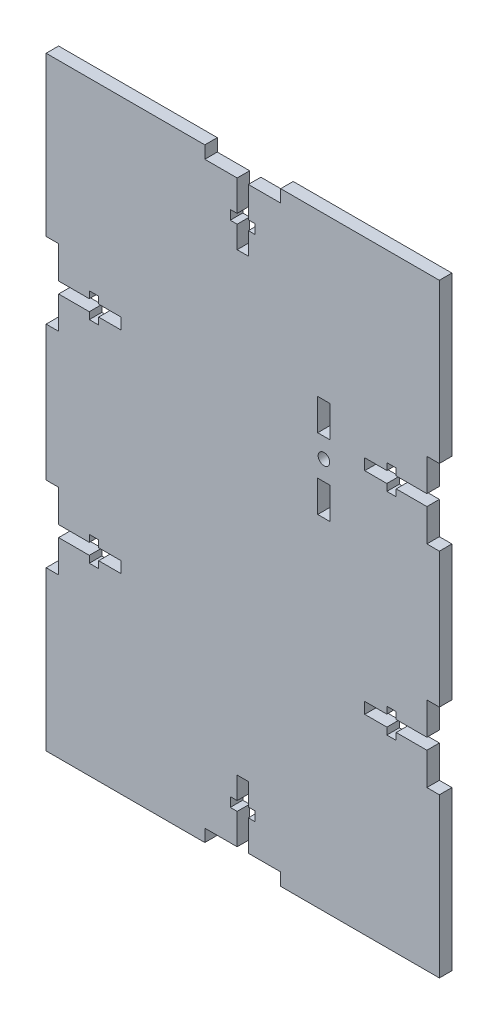
SolidWorks part; units mm, degrees
ref_plane "Front Plane" through (0, 0, 0) normal (0, 0, 1) x (1, 0, 0)
ref_plane "Top Plane" through (0, 0, 0) normal (0, 1, 0) x (1, 0, 0)
ref_plane "Right Plane" through (0, 0, 0) normal (1, 0, 0) x (0, 0, -1)
sketch "Sketch1" plane through (0, 0, 0) normal (0, 0, 1) x (1, 0, 0)
  line L0 (-50, 76.825) -> (-16.6667, 76.825)
  line L1 (-50, -76.825) -> (50, -76.825)
  line L2 (-50, -76.825) -> (-50, 76.825)
  line L3 (-50, 76.825) -> (50, 76.825) construction
  line L4 (50, -76.825) -> (50, 76.825)
  line L5 (-50, -76.825) -> (50, 76.825) construction
  line L6 (-50, 76.825) -> (50, -76.825) construction
  line L7 (-16.6667, 76.825) -> (16.6667, 76.825)
  line L8 (16.6667, 76.825) -> (50, 76.825)
  point P0 (0, 0)
  dimension "D1" = 100
  dimension "D2" = 153.65
extrude "Boss-Extrude1" add sketch "Sketch1" along normal blind 3.18
sketch "Sketch3" [suppressed] plane through (0, 0, 0) normal (0, 0, -1) x (-1, 0, 0)
  line L0 (-32.675, 34.075) -> (-32.675, -61.675)
  line L1 (-32.675, -61.675) -> (32.675, -61.675)
  line L2 (32.675, -61.675) -> (32.675, 34.075)
  line L3 (32.675, 34.075) -> (9.5, 34.075)
  line L4 (9.5, 34.075) -> (9.5, 37.075)
  line L5 (9.5, 37.075) -> (-9.5, 37.075)
  line L6 (-9.5, 37.075) -> (-9.5, 34.075)
  line L7 (-9.5, 34.075) -> (-32.675, 34.075)
  line L8 (32.675, 44.075) -> (-32.675, 44.075)
  line L9 (32.675, -61.675) -> (32.675, 44.075)
  line L10 (-32.675, -61.675) -> (32.675, -61.675)
  line L11 (-32.675, 44.075) -> (-32.675, -61.675)
  line L12 (-32.675, -61.675) -> (-32.675, -73.645) construction
  line L13 (44.645, -73.645) -> (-44.645, -73.645) construction
  line L14 (-32.675, -61.675) -> (-44.645, -61.675) construction
  line L15 (-44.645, -73.645) -> (-44.645, 73.645) construction
  line L16 (32.675, -61.675) -> (44.645, -61.675) construction
  line L17 (44.645, 73.645) -> (44.645, -73.645) construction
  dimension "D1" = 65.35
  dimension "D2" = 95.75
  dimension "D3" = 105.75
  dimension "D4" = 19
  dimension "D5" = 3
extrude "Cut-Extrude1" [suppressed] cut sketch "Sketch3" against normal through all contours L6 L7 L0 L1 L2 L3 L4 L5
sketch "Sketch9" [suppressed] plane through (-44.645, 0, 0) normal (-1, 0, 0) x (0, 0, 1)
  line L0 (0, 0) -> (3.18, 0) construction
  line L1 (0, 73.645) -> (0, -73.645) construction
  line L2 (3.18, 73.645) -> (3.18, -73.645) construction
  line L4 (0, -9.65) -> (3.18, -9.65)
  line L5 (0, -9.65) -> (0, 9.65)
  line L6 (0, 9.65) -> (3.18, 9.65)
  line L7 (3.18, -9.65) -> (3.18, 9.65)
  line L8 (0, -9.65) -> (3.18, 9.65) construction
  line L9 (0, 9.65) -> (3.18, -9.65) construction
  point P6 (1.59, 0)
  dimension "D1" = 19.3
extrude "Boss-Extrude4" [suppressed] add sketch "Sketch9" along normal blind 3.18
sketch "Sketch10" [suppressed] plane through (0, 0, 3.18) normal (0, 0, 1) x (1, 0, 0)
  line L0 (-46.235, 9.65) -> (-46.235, -9.65) construction
  line L1 (-47.825, 9.65) -> (-44.645, 9.65) construction
  line L2 (-47.825, -9.65) -> (-44.645, -9.65) construction
  circle A0 centre (-46.235, 0) radius 1.425
extrude "Cut-Extrude4" [suppressed] cut sketch "Sketch10" against normal through all
mirror "Mirror1" [suppressed] about plane through (0, 0, 0) normal (1, 0, 0)
sketch "Sketch18" [suppressed] plane through (44.645, 0, 0) normal (1, 0, 0) x (0, 0, -1)
  line L0 (0, 0) -> (-3.18, 0) construction
  line L1 (0, -73.645) -> (0, 73.645) construction
  line L2 (-3.18, -73.645) -> (-3.18, 73.645) construction
  line L4 (-3.18, -9.65) -> (0, -9.65)
  line L5 (-3.18, -9.65) -> (-3.18, 9.65)
  line L6 (-3.18, 9.65) -> (0, 9.65)
  line L7 (0, -9.65) -> (0, 9.65)
  line L8 (-3.18, -9.65) -> (0, 9.65) construction
  line L9 (-3.18, 9.65) -> (0, -9.65) construction
  point P6 (-1.59, 0)
  dimension "D1" = 19.3
extrude "Boss-Extrude8" [suppressed] add sketch "Sketch18" along normal blind 3.18
sketch "Sketch19" [suppressed] plane through (0, 0, 3.18) normal (0, 0, 1) x (1, 0, 0)
  line L0 (46.235, -9.65) -> (46.235, 9.65) construction
  line L1 (47.825, -9.65) -> (44.645, -9.65) construction
  line L2 (47.825, 9.65) -> (44.645, 9.65) construction
  circle A0 centre (46.235, 0) radius 1.425
extrude "Cut-Extrude8" [suppressed] cut sketch "Sketch19" against normal through all
mirror "Mirror2" [suppressed] about plane through (0, 0, 0) normal (1, 0, 0)
sketch "Sketch20" plane through (0, 0, 3.18) normal (0, 0, 1) x (1, 0, 0)
  line L0 (0, 70.465) -> (0, 0) construction
  line L1 (50, 76.825) -> (-50, 76.825) construction
  line L2 (-9.65, 76.825) -> (9.65, 76.825)
  line L3 (9.65, 76.825) -> (9.65, 73.645)
  line L4 (9.65, 73.645) -> (1.425, 73.645)
  line L5 (1.425, 73.645) -> (1.425, 65.845)
  line L6 (1.425, 65.845) -> (3.175, 65.845)
  line L7 (3.175, 65.845) -> (3.175, 63.465)
  line L8 (3.175, 63.465) -> (1.425, 63.465)
  line L9 (1.425, 63.465) -> (1.425, 57.845)
  line L10 (1.425, 57.845) -> (-1.425, 57.845)
  line L11 (-1.425, 57.845) -> (-1.425, 63.465)
  line L12 (-1.425, 63.465) -> (-3.175, 63.465)
  line L13 (-3.175, 63.465) -> (-3.175, 65.845)
  line L14 (-3.175, 65.845) -> (-1.425, 65.845)
  line L15 (-1.425, 65.845) -> (-1.425, 73.645)
  line L16 (-1.425, 73.645) -> (-9.65, 73.645)
  line L17 (-9.65, 73.645) -> (-9.65, 76.825)
  dimension "D1" = 19.3
  dimension "D2" = 3.18
  dimension "D3" = 15.8
  dimension "D4" = 6.35
  dimension "D5" = 2.38
  dimension "D6" = 2.85
  dimension "D7" = 7.8
extrude "Cut-Extrude9" cut sketch "Sketch20" against normal through all
mirror "Mirror3" about plane through (0, 0, 0) normal (0, 1, 0) of "Cut-Extrude9"
sketch "Sketch23" plane through (0, 0, 3.18) normal (0, 0, 1) x (1, 0, 0)
  line L0 (-50, 17.175) -> (-50, 36.475)
  line L1 (-50, 76.825) -> (-50, -76.825) construction
  line L2 (-50, 36.475) -> (-46.82, 36.475)
  line L3 (-46.82, 36.475) -> (-46.82, 28.25)
  line L4 (-46.82, 28.25) -> (-39.02, 28.25)
  line L5 (-39.02, 28.25) -> (-39.02, 30)
  line L6 (-39.02, 30) -> (-36.64, 30)
  line L7 (-36.64, 30) -> (-36.64, 28.25)
  line L8 (-36.64, 28.25) -> (-31.02, 28.25)
  line L9 (-31.02, 28.25) -> (-31.02, 25.4)
  line L10 (-31.02, 25.4) -> (-36.64, 25.4)
  line L11 (-36.64, 25.4) -> (-36.64, 23.65)
  line L12 (-36.64, 23.65) -> (-39.02, 23.65)
  line L13 (-39.02, 23.65) -> (-39.02, 25.4)
  line L14 (-39.02, 25.4) -> (-46.82, 25.4)
  line L15 (-46.82, 25.4) -> (-46.82, 17.175)
  line L16 (-46.82, 17.175) -> (-50, 17.175)
  line L17 (-9.65, 76.825) -> (-50, 76.825) construction
  line L19 (-31.02, 26.825) -> (-50, 26.825) construction
  line L20 (-50, -36.475) -> (-50, -17.175)
  line L21 (-50, -17.175) -> (-46.82, -17.175)
  line L22 (-46.82, -17.175) -> (-46.82, -25.4)
  line L23 (-46.82, -25.4) -> (-39.02, -25.4)
  line L24 (-39.02, -25.4) -> (-39.02, -23.65)
  line L25 (-39.02, -23.65) -> (-36.64, -23.65)
  line L26 (-36.64, -23.65) -> (-36.64, -25.4)
  line L27 (-36.64, -25.4) -> (-31.02, -25.4)
  line L28 (-31.02, -25.4) -> (-31.02, -28.25)
  line L29 (-31.02, -28.25) -> (-36.64, -28.25)
  line L30 (-36.64, -28.25) -> (-36.64, -30)
  line L31 (-36.64, -30) -> (-39.02, -30)
  line L32 (-39.02, -30) -> (-39.02, -28.25)
  line L33 (-39.02, -28.25) -> (-46.82, -28.25)
  line L34 (-46.82, -28.25) -> (-46.82, -36.475)
  line L35 (-46.82, -36.475) -> (-50, -36.475)
  line L36 (-50, -26.825) -> (-31.02, -26.825) construction
  line L37 (-50, -76.825) -> (-9.65, -76.825) construction
  dimension "D1" = 50
  dimension "D2" = 19.3
  dimension "D3" = 3.18
  dimension "D4" = 15.8
  dimension "D5" = 6.35
  dimension "D6" = 2.85
  dimension "D7" = 7.8
  dimension "D8" = 2.38
  dimension "D9" = 19.3
  dimension "D10" = 3.18
  dimension "D11" = 7.8
  dimension "D12" = 15.8
  dimension "D13" = 6.35
  dimension "D14" = 2.85
  dimension "D15" = 2.38
  dimension "D16" = 50
  dimension "D17" = 1.75
extrude "Cut-Extrude10" cut sketch "Sketch23" against normal through all
sketch "Sketch24" [suppressed] plane through (0, 0, 3.18) normal (0, 0, 1) x (1, 0, 0)
  line L0 (44.645, -13.995) -> (44.645, -33.295)
  line L1 (44.645, -73.645) -> (44.645, 73.645) construction
  line L2 (44.645, -33.295) -> (41.465, -33.295)
  line L3 (41.465, -33.295) -> (41.465, -25.07)
  line L4 (41.465, -25.07) -> (33.665, -25.07)
  line L5 (33.665, -25.07) -> (33.665, -26.82)
  line L6 (33.665, -26.82) -> (31.285, -26.82)
  line L7 (31.285, -26.82) -> (31.285, -25.07)
  line L8 (31.285, -25.07) -> (25.665, -25.07)
  line L9 (25.665, -25.07) -> (25.665, -22.22)
  line L10 (25.665, -22.22) -> (31.285, -22.22)
  line L11 (31.285, -22.22) -> (31.285, -20.47)
  line L12 (31.285, -20.47) -> (33.665, -20.47)
  line L13 (33.665, -20.47) -> (33.665, -22.22)
  line L14 (33.665, -22.22) -> (41.465, -22.22)
  line L15 (41.465, -22.22) -> (41.465, -13.995)
  line L16 (41.465, -13.995) -> (44.645, -13.995)
  line L17 (25.665, -23.645) -> (44.645, -23.645) construction
  line L18 (-44.645, -73.645) -> (44.645, -73.645) construction
  line L19 (44.645, 33.295) -> (44.645, 13.995)
  line L20 (44.645, 13.995) -> (41.465, 13.995)
  line L21 (41.465, 13.995) -> (41.465, 22.22)
  line L22 (41.465, 22.22) -> (33.665, 22.22)
  line L23 (33.665, 22.22) -> (33.665, 20.47)
  line L24 (33.665, 20.47) -> (31.285, 20.47)
  line L25 (31.285, 20.47) -> (31.285, 22.22)
  line L26 (31.285, 22.22) -> (25.665, 22.22)
  line L27 (25.665, 22.22) -> (25.665, 25.07)
  line L28 (25.665, 25.07) -> (31.285, 25.07)
  line L29 (31.285, 25.07) -> (31.285, 26.82)
  line L30 (31.285, 26.82) -> (33.665, 26.82)
  line L31 (33.665, 26.82) -> (33.665, 25.07)
  line L32 (33.665, 25.07) -> (41.465, 25.07)
  line L33 (41.465, 25.07) -> (41.465, 33.295)
  line L34 (41.465, 33.295) -> (44.645, 33.295)
  line L35 (25.665, 23.645) -> (44.645, 23.645) construction
  line L36 (44.645, 73.645) -> (-44.645, 73.645) construction
  dimension "D1" = 19.3
  dimension "D2" = 3.18
  dimension "D3" = 15.8
  dimension "D4" = 7.8
  dimension "D5" = 6.35
  dimension "D6" = 2.85
  dimension "D7" = 2.38
  dimension "D8" = 50
  dimension "D9" = 19.3
  dimension "D10" = 3.18
  dimension "D11" = 7.8
  dimension "D12" = 15.8
  dimension "D13" = 6.35
  dimension "D14" = 2.85
  dimension "D15" = 2.38
  dimension "D16" = 50
extrude "Cut-Extrude11" [suppressed] cut sketch "Sketch24" against normal through all
sketch "Sketch25" [suppressed] plane through (0, 0, 3.18) normal (0, 0, 1) x (1, 0, 0)
  line L0 (9.65, -73.645) -> (-9.65, -73.645)
  line L1 (-44.645, -73.645) -> (44.645, -73.645) construction
  line L2 (-9.65, -73.645) -> (-9.65, -70.465)
  line L3 (-9.65, -70.465) -> (-1.425, -70.465)
  line L4 (-1.425, -70.465) -> (-1.425, -62.665)
  line L5 (-1.425, -62.665) -> (-3.175, -62.665)
  line L6 (-3.175, -62.665) -> (-3.175, -60.285)
  line L7 (-3.175, -60.285) -> (-1.425, -60.285)
  line L8 (-1.425, -60.285) -> (-1.425, -54.665)
  line L9 (-1.425, -54.665) -> (1.425, -54.665)
  line L10 (1.425, -54.665) -> (1.425, -60.285)
  line L11 (1.425, -60.285) -> (3.175, -60.285)
  line L12 (3.175, -60.285) -> (3.175, -62.665)
  line L13 (3.175, -62.665) -> (1.425, -62.665)
  line L14 (1.425, -62.665) -> (1.425, -70.465)
  line L15 (1.425, -70.465) -> (9.65, -70.465)
  line L16 (9.65, -70.465) -> (9.65, -73.645)
  line L17 (0, -73.645) -> (0, 0) construction
  dimension "D1" = 19.3
  dimension "D2" = 3.18
  dimension "D3" = 15.8
  dimension "D4" = 7.8
  dimension "D5" = 6.35
  dimension "D6" = 2.85
  dimension "D7" = 2.38
extrude "Cut-Extrude12" [suppressed] cut sketch "Sketch25" against normal through all
sketch "Sketch26" [suppressed] plane through (0, 0, 3.18) normal (0, 0, 1) x (1, 0, 0)
  line L0 (-9.65, 73.645) -> (9.65, 73.645)
  line L1 (44.645, 73.645) -> (-44.645, 73.645) construction
  line L2 (9.65, 73.645) -> (9.65, 70.465)
  line L3 (9.65, 70.465) -> (1.425, 70.465)
  line L4 (1.425, 70.465) -> (1.425, 62.665)
  line L5 (1.425, 62.665) -> (3.175, 62.665)
  line L6 (3.175, 62.665) -> (3.175, 60.285)
  line L7 (3.175, 60.285) -> (1.425, 60.285)
  line L8 (1.425, 60.285) -> (1.425, 54.665)
  line L9 (1.425, 54.665) -> (-1.425, 54.665)
  line L10 (-1.425, 54.665) -> (-1.425, 60.285)
  line L11 (-1.425, 60.285) -> (-3.175, 60.285)
  line L12 (-3.175, 60.285) -> (-3.175, 62.665)
  line L13 (-3.175, 62.665) -> (-1.425, 62.665)
  line L14 (-1.425, 62.665) -> (-1.425, 70.465)
  line L15 (-1.425, 70.465) -> (-9.65, 70.465)
  line L16 (-9.65, 70.465) -> (-9.65, 73.645)
  line L17 (0, 73.645) -> (0, -4.4192) construction
  dimension "D1" = 19.3
  dimension "D2" = 3.18
  dimension "D3" = 7.8
  dimension "D4" = 15.8
  dimension "D5" = 6.35
  dimension "D6" = 2.85
  dimension "D7" = 2.38
extrude "Cut-Extrude13" [suppressed] cut sketch "Sketch26" against normal through all
mirror "Mirror4" about plane through (0, 0, 0) normal (1, 0, 0) of "Cut-Extrude10"
mirror "Mirror5" [suppressed] about plane through (0, 0, 0) normal (1, 0, 0)
mirror "Mirror6" [suppressed] about plane through (0, 0, 0) normal (0, 1, 0)
mirror "Mirror7" [suppressed] about plane through (0, 0, 0) normal (0, 1, 0)
sketch "Sketch27" [suppressed] plane through (-44.645, 0, 0) normal (-1, 0, 0) x (0, 0, 1)
  line L0 (0, -36.475) -> (0, -17.175)
  line L1 (0, 73.645) -> (0, -73.645) construction
  line L2 (0, -17.175) -> (3.18, -17.175)
  line L3 (3.18, 73.645) -> (3.18, -73.645) construction
  line L4 (3.18, -17.175) -> (3.18, -36.475)
  line L5 (3.18, -36.475) -> (0, -36.475)
  line L6 (3.18, -26.825) -> (0, -26.825) construction
  line L7 (3.18, -73.645) -> (0, -73.645) construction
  dimension "D1" = 19.3
  dimension "D2" = 46.82
extrude "Boss-Extrude9" [suppressed] add sketch "Sketch27" along normal blind 3.18
sketch "Sketch28" [suppressed] plane through (0, -73.645, 0) normal (0, -1, 0) x (1, 0, 0)
  line L0 (9.65, 0) -> (-9.65, 0)
  line L1 (-44.645, 0) -> (44.645, 0) construction
  line L2 (-9.65, 0) -> (-9.65, 3.18)
  line L3 (-44.645, 3.18) -> (44.645, 3.18) construction
  line L4 (-9.65, 3.18) -> (9.65, 3.18)
  line L5 (9.65, 3.18) -> (9.65, 0)
  line L6 (0, 0) -> (0, 3.18) construction
  dimension "D1" = 19.3
extrude "Boss-Extrude10" [suppressed] add sketch "Sketch28" along normal blind 3.18
sketch "Sketch29" [suppressed] plane through (0, 0, 3.18) normal (0, 0, 1) x (1, 0, 0)
  line L0 (-47.825, -26.825) -> (-37.3062, -26.825) construction
  line L1 (-47.825, -36.475) -> (-47.825, -17.175) construction
  line L2 (-46.235, -17.175) -> (-46.235, -36.475) construction
  line L3 (-47.825, -17.175) -> (-44.645, -17.175) construction
  line L4 (-47.825, -36.475) -> (-44.645, -36.475) construction
  circle A0 centre (-46.235, -26.825) radius 1.425
extrude "Cut-Extrude14" [suppressed] cut sketch "Sketch29" against normal through all
sketch "Sketch30" [suppressed] plane through (0, 0, 3.18) normal (0, 0, 1) x (1, 0, 0)
  line L0 (0, -76.825) -> (0, -66.2855) construction
  line L1 (9.65, -76.825) -> (-9.65, -76.825) construction
  line L2 (9.65, -75.235) -> (-9.65, -75.235) construction
  line L3 (9.65, -76.825) -> (9.65, -73.645) construction
  line L4 (-9.65, -76.825) -> (-9.65, -73.645) construction
  circle A0 centre (0, -75.235) radius 1.425
extrude "Cut-Extrude15" [suppressed] cut sketch "Sketch30" against normal through all
mirror "Mirror8" [suppressed] about plane through (0, 0, 0) normal (1, 0, 0)
mirror "Mirror9" [suppressed] about plane through (0, 0, 0) normal (0, 1, 0)
sketch "Sketch31" [suppressed] plane through (0, 0, 3.18) normal (0, 0, 1) x (1, 0, 0)
  line L0 (14.341, -8.1358) -> (14.341, -12.6358) construction
  line L8 (5.175, -1.9558) -> (5.175, 19.3642) construction
  line L10 (-24.825, 19.3642) -> (-24.825, -1.9558) construction
  line L11 (5.175, 19.3642) -> (-24.825, 19.3642) construction
  line L16 (23.507, -9.6358) -> (39.341, -9.6358) construction
  line L17 (23.507, 19.3642) -> (23.507, -9.6358) construction
  line L18 (39.341, 19.3642) -> (23.507, 19.3642) construction
  line L19 (39.341, -9.6358) -> (39.341, 19.3642) construction
  line L26 (14.341, -15.8158) -> (14.341, -12.6358) construction
  line L29 (-24.825, -1.9558) -> (5.175, -1.9558) construction
  line L34 (20.5772, -7.1358) -> (20.5772, 11.3642) construction
  line L35 (20.5772, 11.3642) -> (8.1048, 11.3642) construction
  line L36 (8.1048, 11.3642) -> (8.1048, -7.1358) construction
  line L37 (9.7431, -8.1358) -> (18.9389, -8.1358) construction
  line L38 (14.341, -15.8158) -> (14.341, -50) construction
  line L39 (-17.325, 9.65) -> (-24.825, 9.65) construction
  line L40 (-6.159, -12.4758) -> (34.841, -12.4758)
  line L41 (-6.159, -12.4758) -> (-6.159, -15.9758)
  line L42 (-6.159, -15.9758) -> (34.841, -15.9758)
  line L43 (34.841, -12.4758) -> (34.841, -15.9758)
  line L88 (-44.645, -50) -> (-9.65, -50) construction
  line L89 (-9.65, -50) -> (-9.65, -46.82) construction
  line L90 (-9.65, -46.82) -> (-1.425, -46.82) construction
  line L91 (-1.425, -46.82) -> (-1.425, -39.02) construction
  line L92 (-1.425, -39.02) -> (-3.175, -39.02) construction
  line L93 (-3.175, -39.02) -> (-3.175, -36.64) construction
  line L94 (-3.175, -36.64) -> (-1.425, -36.64) construction
  line L95 (-1.425, -36.64) -> (-1.425, -31.02) construction
  line L96 (-1.425, -31.02) -> (1.425, -31.02) construction
  line L97 (1.425, -31.02) -> (1.425, -36.64) construction
  line L98 (1.425, -36.64) -> (3.175, -36.64) construction
  line L99 (3.175, -36.64) -> (3.175, -39.02) construction
  line L100 (3.175, -39.02) -> (1.425, -39.02) construction
  line L101 (1.425, -39.02) -> (1.425, -46.82) construction
  line L102 (1.425, -46.82) -> (9.65, -46.82) construction
  line L103 (9.65, -46.82) -> (9.65, -50) construction
  line L104 (9.65, -50) -> (44.645, -50) construction
  line L105 (44.645, -50) -> (44.645, -9.65) construction
  line L106 (44.645, -9.65) -> (47.825, -9.65) construction
  line L107 (47.825, -9.65) -> (47.825, 9.65) construction
  line L108 (47.825, 9.65) -> (44.645, 9.65) construction
  line L109 (44.645, 9.65) -> (44.645, 50) construction
  line L110 (44.645, 50) -> (9.65, 50) construction
  line L111 (9.65, 50) -> (9.65, 46.82) construction
  line L112 (9.65, 46.82) -> (1.425, 46.82) construction
  line L113 (1.425, 46.82) -> (1.425, 39.02) construction
  line L114 (1.425, 39.02) -> (3.175, 39.02) construction
  line L115 (3.175, 39.02) -> (3.175, 36.64) construction
  line L116 (3.175, 36.64) -> (1.425, 36.64) construction
  line L117 (1.425, 36.64) -> (1.425, 31.02) construction
  line L118 (1.425, 31.02) -> (-1.425, 31.02) construction
  line L119 (-1.425, 31.02) -> (-1.425, 36.64) construction
  line L120 (-1.425, 36.64) -> (-3.175, 36.64) construction
  line L121 (-3.175, 36.64) -> (-3.175, 39.02) construction
  line L122 (-3.175, 39.02) -> (-1.425, 39.02) construction
  line L123 (-1.425, 39.02) -> (-1.425, 46.82) construction
  line L124 (-1.425, 46.82) -> (-9.65, 46.82) construction
  line L125 (-9.65, 46.82) -> (-9.65, 50) construction
  line L126 (-9.65, 50) -> (-44.645, 50) construction
  line L127 (-44.645, 50) -> (-44.645, 9.65) construction
  line L128 (-44.645, 9.65) -> (-47.825, 9.65) construction
  line L129 (-47.825, 9.65) -> (-47.825, -9.65) construction
  line L130 (-47.825, -9.65) -> (-44.645, -9.65) construction
  line L131 (-44.645, -9.65) -> (-44.645, -50) construction
  line L132 (-6.159, -12.4758) -> (34.841, -15.9758) construction
  line L133 (-6.159, -15.9758) -> (34.841, -12.4758) construction
  line L134 (-17.325, 9.65) -> (-17.325, -1.9558) construction
  line L135 (31.3061, 4.8642) -> (39.341, 4.8642) construction
  line L136 (31.3061, 4.8642) -> (31.3061, 19.3642) construction
  line L137 (-17.325, 9.65) -> (-4.325, 9.65) construction
  circle A0 centre (-17.325, 9.65) radius 1.5
  circle A1 centre (31.3061, 4.8642) radius 1.5
  circle A2 centre (-4.325, 9.65) radius 1.5
  spline S4 degree 3 poles (8.1048, -7.1358) (8.1048, -7.3148) (8.1799, -7.485) (8.4092, -7.7556) (8.5582, -7.8571) (8.8762, -8.0081) (9.0479, -8.0586) (9.3919, -8.1221) (9.5665, -8.1358) (9.7431, -8.1358) knots 0 0 0 0 0.25 0.25 0.5 0.5 0.75 0.75 1 1 1 1 construction
  spline S5 degree 3 poles (18.9389, -8.1358) (19.1156, -8.1358) (19.2906, -8.1221) (19.6363, -8.0581) (19.8071, -8.0076) (20.1239, -7.857) (20.2729, -7.7556) (20.5025, -7.4843) (20.5772, -7.3148) (20.5772, -7.1358) knots 0 0 0 0 0.25 0.25 0.5 0.5 0.75 0.75 1 1 1 1 construction
  point P14 (14.341, -14.2258)
  point P46 (-44.645, 73.645)
  dimension "D6" = 3
  dimension "D4" = 41
  dimension "D5" = 3.5
  dimension "D7" = 7.5
  dimension "D9" = 13
extrude "Cut-Extrude16" [suppressed] cut sketch "Sketch31" against normal through all contours L41 L40 L43 L42 | A1 | A2 | A0
sketch "Sketch32" plane through (0, 0, 3.18) normal (0, 0, 1) x (1, 0, 0)
  line L0 (22.24, 17.7829) -> (22.24, 9.7829)
  line L1 (22.24, 35.7829) -> (22.24, 27.7829)
  line L2 (22.24, 35.7829) -> (19.06, 35.7829)
  line L3 (22.24, 35.7829) -> (22.24, 27.7829)
  line L4 (22.24, 27.7829) -> (19.06, 27.7829)
  line L5 (19.06, 35.7829) -> (19.06, 27.7829)
  line L6 (22.24, 17.7829) -> (19.06, 17.7829)
  line L7 (22.24, 17.7829) -> (22.24, 9.7829)
  line L8 (22.24, 9.7829) -> (19.06, 9.7829)
  line L9 (19.06, 17.7829) -> (19.06, 9.7829)
  line L10 (22.24, 17.7829) -> (22.24, 27.7829) construction
  line L11 (50, -17.175) -> (50, 17.175) construction
  line L12 (50, 17.175) -> (46.82, 17.175) construction
  line L13 (46.82, 17.175) -> (46.82, 25.4) construction
  line L14 (46.82, 25.4) -> (39.02, 25.4) construction
  line L15 (39.02, 25.4) -> (39.02, 23.65) construction
  line L16 (39.02, 23.65) -> (36.64, 23.65) construction
  line L17 (36.64, 23.65) -> (36.64, 25.4) construction
  line L18 (36.64, 25.4) -> (31.02, 25.4) construction
  line L19 (31.02, 25.4) -> (31.02, 28.25) construction
  line L20 (31.02, 28.25) -> (36.64, 28.25) construction
  line L21 (36.64, 28.25) -> (36.64, 30) construction
  line L22 (36.64, 30) -> (39.02, 30) construction
  line L23 (39.02, 30) -> (39.02, 28.25) construction
  line L24 (39.02, 28.25) -> (46.82, 28.25) construction
  line L25 (46.82, 28.25) -> (46.82, 36.475) construction
  line L26 (46.82, 36.475) -> (50, 36.475) construction
  line L27 (50, 36.475) -> (50, 76.825) construction
  line L28 (50, 76.825) -> (9.65, 76.825) construction
  line L29 (9.65, 76.825) -> (9.65, 73.645) construction
  line L30 (9.65, 73.645) -> (1.425, 73.645) construction
  line L31 (1.425, 73.645) -> (1.425, 65.845) construction
  line L32 (1.425, 65.845) -> (3.175, 65.845) construction
  line L33 (3.175, 65.845) -> (3.175, 63.465) construction
  line L34 (3.175, 63.465) -> (1.425, 63.465) construction
  line L35 (1.425, 63.465) -> (1.425, 57.845) construction
  line L36 (1.425, 57.845) -> (-1.425, 57.845) construction
  line L37 (-1.425, 57.845) -> (-1.425, 63.465) construction
  line L38 (-1.425, 63.465) -> (-3.175, 63.465) construction
  line L39 (-3.175, 63.465) -> (-3.175, 65.845) construction
  line L40 (-3.175, 65.845) -> (-1.425, 65.845) construction
  line L41 (-1.425, 65.845) -> (-1.425, 73.645) construction
  line L42 (-1.425, 73.645) -> (-9.65, 73.645) construction
  line L43 (-9.65, 73.645) -> (-9.65, 76.825) construction
  line L44 (-9.65, 76.825) -> (-50, 76.825) construction
  line L45 (-50, 76.825) -> (-50, 36.475) construction
  line L46 (-50, 36.475) -> (-46.82, 36.475) construction
  line L47 (-46.82, 36.475) -> (-46.82, 28.25) construction
  line L48 (-46.82, 28.25) -> (-39.02, 28.25) construction
  line L49 (-39.02, 28.25) -> (-39.02, 30) construction
  line L50 (-39.02, 30) -> (-36.64, 30) construction
  line L51 (-36.64, 30) -> (-36.64, 28.25) construction
  line L52 (-36.64, 28.25) -> (-31.02, 28.25) construction
  line L53 (-31.02, 28.25) -> (-31.02, 25.4) construction
  line L54 (-31.02, 25.4) -> (-36.64, 25.4) construction
  line L55 (-36.64, 25.4) -> (-36.64, 23.65) construction
  line L56 (-36.64, 23.65) -> (-39.02, 23.65) construction
  line L57 (-39.02, 23.65) -> (-39.02, 25.4) construction
  line L58 (-39.02, 25.4) -> (-46.82, 25.4) construction
  line L59 (-46.82, 25.4) -> (-46.82, 17.175) construction
  line L60 (-46.82, 17.175) -> (-50, 17.175) construction
  line L61 (-50, 17.175) -> (-50, -17.175) construction
  line L62 (-50, -17.175) -> (-46.82, -17.175) construction
  line L63 (-46.82, -17.175) -> (-46.82, -25.4) construction
  line L64 (-46.82, -25.4) -> (-39.02, -25.4) construction
  line L65 (-39.02, -25.4) -> (-39.02, -23.65) construction
  line L66 (-39.02, -23.65) -> (-36.64, -23.65) construction
  line L67 (-36.64, -23.65) -> (-36.64, -25.4) construction
  line L68 (-36.64, -25.4) -> (-31.02, -25.4) construction
  line L69 (-31.02, -25.4) -> (-31.02, -28.25) construction
  line L70 (-31.02, -28.25) -> (-36.64, -28.25) construction
  line L71 (-36.64, -28.25) -> (-36.64, -30) construction
  line L72 (-36.64, -30) -> (-39.02, -30) construction
  line L73 (-39.02, -30) -> (-39.02, -28.25) construction
  line L74 (-39.02, -28.25) -> (-46.82, -28.25) construction
  line L75 (-46.82, -28.25) -> (-46.82, -36.475) construction
  line L76 (-46.82, -36.475) -> (-50, -36.475) construction
  line L77 (-50, -36.475) -> (-50, -76.825) construction
  line L78 (-50, -76.825) -> (-9.65, -76.825) construction
  line L79 (-9.65, -76.825) -> (-9.65, -73.645) construction
  line L80 (-9.65, -73.645) -> (-1.425, -73.645) construction
  line L81 (-1.425, -73.645) -> (-1.425, -65.845) construction
  line L82 (-1.425, -65.845) -> (-3.175, -65.845) construction
  line L83 (-3.175, -65.845) -> (-3.175, -63.465) construction
  line L84 (-3.175, -63.465) -> (-1.425, -63.465) construction
  line L85 (-1.425, -63.465) -> (-1.425, -57.845) construction
  line L86 (-1.425, -57.845) -> (1.425, -57.845) construction
  line L87 (1.425, -57.845) -> (1.425, -63.465) construction
  line L88 (1.425, -63.465) -> (3.175, -63.465) construction
  line L89 (3.175, -63.465) -> (3.175, -65.845) construction
  line L90 (3.175, -65.845) -> (1.425, -65.845) construction
  line L91 (1.425, -65.845) -> (1.425, -73.645) construction
  line L92 (1.425, -73.645) -> (9.65, -73.645) construction
  line L93 (9.65, -73.645) -> (9.65, -76.825) construction
  line L94 (9.65, -76.825) -> (50, -76.825) construction
  line L95 (50, -76.825) -> (50, -36.475) construction
  line L96 (50, -36.475) -> (46.82, -36.475) construction
  line L97 (46.82, -36.475) -> (46.82, -28.25) construction
  line L98 (46.82, -28.25) -> (39.02, -28.25) construction
  line L99 (39.02, -28.25) -> (39.02, -30) construction
  line L100 (39.02, -30) -> (36.64, -30) construction
  line L101 (36.64, -30) -> (36.64, -28.25) construction
  line L102 (36.64, -28.25) -> (31.02, -28.25) construction
  line L103 (31.02, -28.25) -> (31.02, -25.4) construction
  line L104 (31.02, -25.4) -> (36.64, -25.4) construction
  line L105 (36.64, -25.4) -> (36.64, -23.65) construction
  line L106 (36.64, -23.65) -> (39.02, -23.65) construction
  line L107 (39.02, -23.65) -> (39.02, -25.4) construction
  line L108 (39.02, -25.4) -> (46.82, -25.4) construction
  line L109 (46.82, -25.4) -> (46.82, -17.175) construction
  line L110 (46.82, -17.175) -> (50, -17.175) construction
  line L111 (20.65, 27.7829) -> (20.65, 17.7829) construction
  line L112 (0, 0) -> (0, 57.845) construction
  line L113 (-20.65, 27.7829) -> (-20.65, 17.7829) construction
  line L114 (-22.24, 17.7829) -> (-22.24, 27.7829) construction
  line L115 (-19.06, 17.7829) -> (-19.06, 9.7829)
  line L116 (-22.24, 9.7829) -> (-19.06, 9.7829)
  line L117 (-22.24, 17.7829) -> (-22.24, 9.7829)
  line L118 (-22.24, 17.7829) -> (-19.06, 17.7829)
  line L119 (-19.06, 35.7829) -> (-19.06, 27.7829)
  line L120 (-22.24, 27.7829) -> (-19.06, 27.7829)
  line L121 (-22.24, 35.7829) -> (-22.24, 27.7829)
  line L122 (-22.24, 35.7829) -> (-19.06, 35.7829)
  line L123 (-22.24, 35.7829) -> (-22.24, 27.7829)
  line L124 (-22.24, 17.7829) -> (-22.24, 9.7829)
  circle A0 centre (20.65, 22.7829) radius 1.47
  circle A1 centre (-20.65, 22.7829) radius 1.47
  dimension "D1" = 2.94
extrude "Cut-Extrude17" [suppressed] cut sketch "Sketch32" against normal through all contours L118 L117 L116 L115 | L122 L121 L120 L119 | A1
extrude "Cut-Extrude18" cut sketch "Sketch32<4>" against normal through all contours L2 L5 L4 L1 | A0 | L6 L9 L8 L0 region at (20.65, 13.7829, 3.18) region at (20.65, 31.7829, 3.18) region at (20.65, 22.7829, 3.18)
sketch "Sketch32<4>" plane through (0, 0, 3.18) normal (0, 0, 1) x (1, 0, 0) same geometry as "Sketch32"
sketch "Sketch33" plane through (0, 0, 0) normal (0, 0, 1) x (1, 0, 0)
  line L108 (-49.2618, -106.2706) -> (-49.2618, -114.2706)
  line L109 (-49.2618, -114.2706) -> (-46.0818, -114.2706)
  line L110 (-46.0818, -114.2706) -> (-46.0818, -106.2706)
  line L111 (-46.0818, -106.2706) -> (-49.2618, -106.2706)
  line L112 (-49.2618, -55.6706) -> (-49.2618, -63.6706)
  line L113 (-49.2618, -63.6706) -> (-46.0818, -63.6706)
  line L114 (-46.0818, -63.6706) -> (-46.0818, -55.6706)
  line L115 (-46.0818, -55.6706) -> (-49.2618, -55.6706)
  line L116 (23.8582, -78.6341) -> (23.8582, -44.2841)
  line L117 (23.8582, -44.2841) -> (20.6782, -44.2841)
  line L118 (20.6782, -44.2841) -> (20.6782, -36.0591)
  line L119 (20.6782, -36.0591) -> (12.8782, -36.0591)
  line L120 (12.8782, -36.0591) -> (12.8782, -37.8091)
  line L121 (12.8782, -37.8091) -> (10.4982, -37.8091)
  line L122 (10.4982, -37.8091) -> (10.4982, -36.0591)
  line L123 (10.4982, -36.0591) -> (4.8782, -36.0591)
  line L124 (4.8782, -36.0591) -> (4.8782, -33.2091)
  line L125 (4.8782, -33.2091) -> (10.4982, -33.2091)
  line L126 (10.4982, -33.2091) -> (10.4982, -31.4591)
  line L127 (10.4982, -31.4591) -> (12.8782, -31.4591)
  line L128 (12.8782, -31.4591) -> (12.8782, -33.2091)
  line L129 (12.8782, -33.2091) -> (20.6782, -33.2091)
  line L130 (20.6782, -33.2091) -> (20.6782, -24.9841)
  line L131 (20.6782, -24.9841) -> (23.8582, -24.9841)
  line L132 (23.8582, -24.9841) -> (23.8582, 15.3659)
  line L133 (23.8582, 15.3659) -> (-16.4918, 15.3659)
  line L134 (-16.4918, 15.3659) -> (-16.4918, 12.1859)
  line L135 (-16.4918, 12.1859) -> (-24.7168, 12.1859)
  line L136 (-24.7168, 12.1859) -> (-24.7168, 4.3859)
  line L137 (-24.7168, 4.3859) -> (-22.9668, 4.3859)
  line L138 (-22.9668, 4.3859) -> (-22.9668, 2.0059)
  line L139 (-22.9668, 2.0059) -> (-24.7168, 2.0059)
  line L140 (-24.7168, 2.0059) -> (-24.7168, -3.6141)
  line L141 (-24.7168, -3.6141) -> (-27.5668, -3.6141)
  line L142 (-27.5668, -3.6141) -> (-27.5668, 2.0059)
  line L143 (-27.5668, 2.0059) -> (-29.3168, 2.0059)
  line L144 (-29.3168, 2.0059) -> (-29.3168, 4.3859)
  line L145 (-29.3168, 4.3859) -> (-27.5668, 4.3859)
  line L146 (-27.5668, 4.3859) -> (-27.5668, 12.1859)
  line L147 (-27.5668, 12.1859) -> (-35.7918, 12.1859)
  line L148 (-35.7918, 12.1859) -> (-35.7918, 15.3659)
  line L149 (-35.7918, 15.3659) -> (-76.1418, 15.3659)
  line L150 (-76.1418, 15.3659) -> (-76.1418, -24.9841)
  line L151 (-76.1418, -24.9841) -> (-72.9618, -24.9841)
  line L152 (-72.9618, -24.9841) -> (-72.9618, -33.2091)
  line L153 (-72.9618, -33.2091) -> (-65.1618, -33.2091)
  line L154 (-65.1618, -33.2091) -> (-65.1618, -31.4591)
  line L155 (-65.1618, -31.4591) -> (-62.7818, -31.4591)
  line L156 (-62.7818, -31.4591) -> (-62.7818, -33.2091)
  line L157 (-62.7818, -33.2091) -> (-57.1618, -33.2091)
  line L158 (-57.1618, -33.2091) -> (-57.1618, -36.0591)
  line L159 (-57.1618, -36.0591) -> (-62.7818, -36.0591)
  line L160 (-62.7818, -36.0591) -> (-62.7818, -37.8091)
  line L161 (-62.7818, -37.8091) -> (-65.1618, -37.8091)
  line L162 (-65.1618, -37.8091) -> (-65.1618, -36.0591)
  line L163 (-65.1618, -36.0591) -> (-72.9618, -36.0591)
  line L164 (-72.9618, -36.0591) -> (-72.9618, -44.2841)
  line L165 (-72.9618, -44.2841) -> (-76.1418, -44.2841)
  line L166 (-76.1418, -44.2841) -> (-76.1418, -78.6341)
  line L167 (-76.1418, -78.6341) -> (-72.9618, -78.6341)
  line L168 (-72.9618, -78.6341) -> (-72.9618, -86.8591)
  line L169 (-72.9618, -86.8591) -> (-65.1618, -86.8591)
  line L170 (-65.1618, -86.8591) -> (-65.1618, -85.1091)
  line L171 (-65.1618, -85.1091) -> (-62.7818, -85.1091)
  line L172 (-62.7818, -85.1091) -> (-62.7818, -86.8591)
  line L173 (-62.7818, -86.8591) -> (-57.1618, -86.8591)
  line L174 (-57.1618, -86.8591) -> (-57.1618, -89.7091)
  line L175 (-57.1618, -89.7091) -> (-62.7818, -89.7091)
  line L176 (-62.7818, -89.7091) -> (-62.7818, -91.4591)
  line L177 (-62.7818, -91.4591) -> (-65.1618, -91.4591)
  line L178 (-65.1618, -91.4591) -> (-65.1618, -89.7091)
  line L179 (-65.1618, -89.7091) -> (-72.9618, -89.7091)
  line L180 (-72.9618, -89.7091) -> (-72.9618, -97.9341)
  line L181 (-72.9618, -97.9341) -> (-76.1418, -97.9341)
  line L182 (-76.1418, -97.9341) -> (-76.1418, -138.2841)
  line L183 (-76.1418, -138.2841) -> (-35.7918, -138.2841)
  line L184 (-35.7918, -138.2841) -> (-35.7918, -135.1041)
  line L185 (-35.7918, -135.1041) -> (-27.5668, -135.1041)
  line L186 (-27.5668, -135.1041) -> (-27.5668, -127.3041)
  line L187 (-27.5668, -127.3041) -> (-29.3168, -127.3041)
  line L188 (-29.3168, -127.3041) -> (-29.3168, -124.9241)
  line L189 (-29.3168, -124.9241) -> (-27.5668, -124.9241)
  line L190 (-27.5668, -124.9241) -> (-27.5668, -119.3041)
  line L191 (-27.5668, -119.3041) -> (-24.7168, -119.3041)
  line L192 (-24.7168, -119.3041) -> (-24.7168, -124.9241)
  line L193 (-24.7168, -124.9241) -> (-22.9668, -124.9241)
  line L194 (-22.9668, -124.9241) -> (-22.9668, -127.3041)
  line L195 (-22.9668, -127.3041) -> (-24.7168, -127.3041)
  line L196 (-24.7168, -127.3041) -> (-24.7168, -135.1041)
  line L197 (-24.7168, -135.1041) -> (-16.4918, -135.1041)
  line L198 (-16.4918, -135.1041) -> (-16.4918, -138.2841)
  line L199 (-16.4918, -138.2841) -> (23.8582, -138.2841)
  line L200 (23.8582, -138.2841) -> (23.8582, -97.9341)
  line L201 (23.8582, -97.9341) -> (20.6782, -97.9341)
  line L202 (20.6782, -97.9341) -> (20.6782, -89.7091)
  line L203 (20.6782, -89.7091) -> (12.8782, -89.7091)
  line L204 (12.8782, -89.7091) -> (12.8782, -91.4591)
  line L205 (12.8782, -91.4591) -> (10.4982, -91.4591)
  line L206 (10.4982, -91.4591) -> (10.4982, -89.7091)
  line L207 (10.4982, -89.7091) -> (4.8782, -89.7091)
  line L208 (4.8782, -89.7091) -> (4.8782, -86.8591)
  line L209 (4.8782, -86.8591) -> (10.4982, -86.8591)
  line L210 (10.4982, -86.8591) -> (10.4982, -85.1091)
  line L211 (10.4982, -85.1091) -> (12.8782, -85.1091)
  line L212 (12.8782, -85.1091) -> (12.8782, -86.8591)
  line L213 (12.8782, -86.8591) -> (20.6782, -86.8591)
  line L214 (20.6782, -86.8591) -> (20.6782, -78.6341)
  line L215 (20.6782, -78.6341) -> (23.8582, -78.6341)
